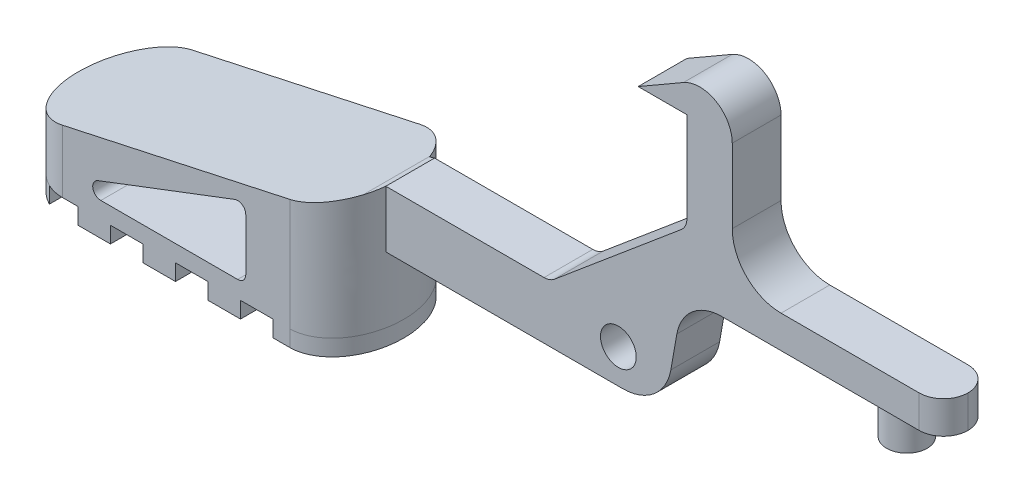
SolidWorks part; units mm, degrees
ref_plane "Alzado" through (0, 0, 0) normal (0, 0, 1) x (1, 0, 0)
ref_plane "Planta" through (0, 0, 0) normal (0, 1, 0) x (1, 0, 0)
ref_plane "Vista lateral" through (0, 0, 0) normal (1, 0, 0) x (0, 0, -1)
sketch "Croquis1" plane through (0, 0, 0) normal (0, 0, 1) x (1, 0, 0)
  line L0 (-3, -7.5922) -> (13, -7.5922)
  line L1 (13, -7.5922) -> (13, -5.5922)
  line L2 (13, -5.5922) -> (0, -5.5922)
  line L3 (-3, -7.5922) -> (-4.2155, -14.4859)
  line L4 (-4.2155, -14.4859) -> (-21.2155, -14.4859)
  line L5 (-21.2155, -14.4859) -> (-21.2155, -10.9859)
  line L6 (-21.2155, -10.9859) -> (-11.2155, -10.9859)
  line L7 (-11.2155, -10.9859) -> (-2.789, -3.9152)
  line L8 (-2.789, -3.9152) -> (-2.789, 2.0848)
  line L9 (-2.789, 2.0848) -> (-5.789, 2.0848)
  line L10 (-5.789, 2.0848) -> (0, 5.4271)
  line L11 (0, -5.5922) -> (0, 5.4271)
  dimension "D1" = 16
  dimension "D2" = 2
  dimension "D3" = 13
  dimension "D4" = 100
  dimension "D5" = 7
  dimension "D6" = 17
  dimension "D7" = 3.5
  dimension "D8" = 10
  dimension "D9" = 140
  dimension "D10" = 11
  dimension "D11" = 6
  dimension "D12" = 3
  dimension "D13" = 30
extrude "Saliente-Extruir1" add sketch "Croquis1" along normal blind 3
fillet "Redondeo1" radius 2 1 edges at (0, 5.4271, 1.5)
fillet "Redondeo2" radius 3 1 edges at (0, -5.5922, 1.5)
fillet "Redondeo3" radius 1.5 2 edges at (13, -6.5922, 3) (13, -6.5922, 0)
fillet "Redondeo4" radius 2.8 1 edges at (-3, -7.5922, 1.5)
fillet "Redondeo5" radius 1 2 edges at (-11.2155, -10.9859, 1.5) (-2.789, -3.9152, 1.5)
sketch "Croquis2" plane through (0, -7.5922, 0) normal (0, -1, 0) x (1, 0, 0)
  line L0 (10.5, 1.5084) -> (13, 1.5) construction
  circle A0 centre (9.25, 1.5084) radius 1.25
  dimension "D1" = 2.5
extrude "Saliente-Extruir2" add sketch "Croquis2" along normal blind 2.2
sketch "Croquis3" plane through (0, 0, 3) normal (0, 0, 1) x (1, 0, 0)
  line L0 (-5.9051, -12.3859) -> (-3.8453, -12.3859) construction
  line L1 (-4.2155, -14.4859) -> (-3.408, -9.906) construction
  line L2 (-7.0051, -13.4859) -> (-7.0051, -14.4859) construction
  line L3 (-21.2155, -14.4859) -> (-4.2155, -14.4859) construction
  circle A0 centre (-7.0051, -12.3859) radius 1.1
  dimension "D1" = 2.2
extrude "Cortar-Extruir1" cut sketch "Croquis3" against normal through all
fillet "Redondeo6" radius 3 1 edges at (-4.2155, -14.4859, 1.5)
sketch "Croquis4" plane through (0, 0, 3) normal (0, 0, 1) x (1, 0, 0)
  line L0 (-21.2155, -14.4859) -> (-21.2155, -18.5345)
  line L1 (-21.2155, -18.5345) -> (-41.2155, -18.5345)
  line L3 (-21.2155, -10.9859) -> (-21.2155, -14.4859)
  line L4 (-41.2155, -18.5345) -> (-41.2155, -15.3345)
  line L5 (-41.2155, -15.3345) -> (-21.2155, -10.9859)
  dimension "D1" = 3.2
extrude "Saliente-Extruir3" add sketch "Croquis4" along normal blind 3 separate body
sketch "Croquis5" plane through (0, 0, 3) normal (0, 0, -1) x (-1, 0, 0)
  line L6 (41.2155, -15.3345) -> (21.2155, -10.9859)
  line L7 (21.2155, -10.9859) -> (21.2155, -18.5345)
  line L8 (21.2155, -18.5345) -> (41.2155, -18.5345)
  line L10 (21.2155, -10.9859) -> (21.2155, -18.5345)
  line L11 (21.2155, -18.5345) -> (41.2155, -18.5345)
  line L13 (41.2155, -15.3345) -> (21.2155, -10.9859)
  line L14 (41.2155, -18.5345) -> (41.2155, -15.3345)
  line L15 (41.2155, -18.5345) -> (41.2155, -15.3345)
  dimension "D1" = 0
extrude "Saliente-Extruir4" add sketch "Croquis5" along normal blind 5
sketch "Croquis6" plane through (0, -18.5345, 0) normal (0, -1, 0) x (1, 0, 0)
  line L0 (-38.2155, 6) -> (-24.2155, 6) construction
  line L1 (-24.2155, 6) -> (-21.2155, 6)
  line L2 (-41.2155, 6) -> (-21.2155, 6) construction
  line L3 (-21.2155, 6) -> (-21.2155, 2)
  line L4 (-24.2155, 6) -> (-24.2155, -2) construction
  line L5 (-21.2155, -2) -> (-41.2155, -2) construction
  line L6 (-24.2155, -2) -> (-38.2155, -2) construction
  line L7 (-38.2155, -2) -> (-38.2155, 6) construction
  line L8 (-38.2155, 2) -> (-41.2155, 2) construction
  line L9 (-41.2155, -2) -> (-41.2155, 6) construction
  line L10 (-24.2155, 2) -> (-21.2155, 2) construction
  line L11 (-21.2155, -2) -> (-21.2155, 6) construction
  line L12 (-41.2155, 2) -> (-41.2155, 6)
  line L13 (-41.2155, 6) -> (-38.2155, 6)
  line L14 (-38.2155, -2) -> (-41.2155, -2)
  line L15 (-41.2155, -2) -> (-41.2155, 2)
  line L16 (-24.2155, -2) -> (-21.2155, -2)
  line L17 (-21.2155, -2) -> (-21.2155, 2)
  ellipse E0 centre (-38.2155, 2) end of major axis (-38.2155, -2) minor radius 3 (-38.2155, 6) -> (-41.2155, 2) ccw
  ellipse E1 centre (-38.2155, 2) end of major axis (-38.2155, -2) minor radius 3 (-38.2155, -2) -> (-41.2155, 2) cw
  ellipse E2 centre (-24.2155, 2) end of major axis (-24.2155, 6) minor radius 3 (-21.2155, 2) -> (-24.2155, 6) ccw
  ellipse E3 centre (-24.2155, 2) end of major axis (-24.2155, 6) minor radius 3 (-24.2155, -2) -> (-21.2155, 2) ccw
  dimension "D1" = 14
extrude "Cortar-Extruir2" cut sketch "Croquis6" against normal blind 5 contours L12 L13 E0
sketch "Croquis7" plane through (0, -18.5345, 0) normal (0, -1, 0) x (1, 0, 0)
  line L0 (-38.2155, -2) -> (-38.2155, 6) construction
  line L1 (-41.2155, 2) -> (-41.2155, -2)
  line L2 (-41.2155, -2) -> (-38.2155, -2)
  ellipse E0 centre (-38.2155, 2) end of major axis (-38.2155, -2) minor radius 3 (-38.2155, -2) -> (-41.2155, 2) cw
extrude "Cortar-Extruir3" cut sketch "Croquis7" against normal blind 5
sketch "Croquis8" plane through (0, -18.5345, 0) normal (0, -1, 0) x (1, 0, 0)
  line L0 (-24.2155, 6) -> (-24.2155, -2) construction
  line L1 (-24.2155, 6) -> (-21.2155, 6)
  line L2 (-21.2155, 6) -> (-21.2155, 2)
  ellipse E0 centre (-24.2155, 2) end of major axis (-24.2155, 6) minor radius 3 (-24.2155, 6) -> (-21.2155, 2) cw
extrude "Cortar-Extruir4" cut sketch "Croquis8" against normal through all
sketch "Croquis9" plane through (0, -18.5345, 0) normal (0, -1, 0) x (1, 0, 0)
  line L0 (-24.2155, 6) -> (-24.2155, -2) construction
  line L1 (-24.2155, -2) -> (-21.2155, -2)
  line L2 (-21.2155, -2) -> (-21.2155, 2)
  ellipse E0 centre (-24.2155, 2) end of major axis (-24.2155, 6) minor radius 3 (-24.2155, -2) -> (-21.2155, 2) ccw
extrude "Cortar-Extruir5" cut sketch "Croquis9" against normal through all
sketch "Croquis10" plane through (-21.2155, 0, 0) normal (-1, 0, 0) x (0, 0, 1)
  line L8 (3, -10.9859) -> (0, -10.9859)
  line L9 (0, -10.9859) -> (0, -14.4859)
  line L10 (0, -14.4859) -> (3, -14.4859)
  line L11 (3, -14.4859) -> (3, -10.9859)
  line L12 (3, -10.9859) -> (0, -10.9859)
  line L13 (0, -10.9859) -> (0, -14.4859)
  line L14 (0, -14.4859) -> (3, -14.4859)
  line L15 (3, -14.4859) -> (3, -10.9859)
  dimension "D1" = 0
extrude "Saliente-Extruir5" add sketch "Croquis10" along normal blind 1
sketch "Croquis12" plane through (0, 0, 3) normal (0, 0, 1) x (1, 0, 0)
  line L0 (-22.2155, -10.9859) -> (-22.2155, -11.2033)
  line L1 (-22.2155, -11.2033) -> (-21.3108, -11.0066)
  line L2 (-21.3108, -11.0066) -> (-21.3108, -10.9859)
  line L3 (-11.5795, -10.9859) -> (-22.2155, -10.9859) construction
  line L4 (-21.3108, -10.9859) -> (-22.2155, -10.9859)
extrude "Cortar-Extruir7" cut sketch "Croquis12" against normal through all
fillet "Redondeo7" radius 3 1 edges at (-21.3108, -11.0066, 1.5)
sketch "Croquis13" plane through (0, 0, 6) normal (0, 0, 1) x (1, 0, 0)
  line L0 (-26.9265, -13.8036) -> (-26.9265, -17.0095)
  line L1 (-27.4265, -17.5095) -> (-35.842, -17.5095)
  line L2 (-36.02, -16.5422) -> (-27.6045, -13.3363)
  arc A0 (-35.842, -17.5095) -> (-36.02, -16.5422) centre (-35.842, -17.0095) cw
  arc A1 (-26.9265, -13.8036) -> (-27.6045, -13.3363) centre (-27.4265, -13.8036) ccw
  arc A2 (-26.9265, -17.0095) -> (-27.4265, -17.5095) centre (-27.4265, -17.0095) cw
  dimension "D1" = 0.5
  dimension "D2" = 0.5
extrude "Cortar-Extruir8" cut sketch "Croquis13" against normal through all
sketch "Croquis14" plane through (0, -18.5345, 0) normal (0, -1, 0) x (1, 0, 0)
  line L0 (-39.251, -1.7542) -> (-39.251, 5.7542)
  line L3 (-39.251, 2) -> (-41.2155, 2) construction
  ellipse E0 centre (-38.2155, 2) end of major axis (-38.2155, -2) minor radius 3 (-38.2155, 6) -> (-38.2155, -2) ccw construction
  spline S0 degree 3 poles (-39.251, 5.7542) (-39.7861, 5.4916) (-40.4667, 4.7951) (-40.9621, 3.6978) (-41.2133, 2.6589) (-41.2465, 1.5628) (-40.9914, 0.3226) (-40.4164, -0.8701) (-39.7097, -1.5293) (-39.251, -1.7542) knots 0 0 0 0 0.199693 0.316984 0.40333 0.559671 0.682683 0.828477 1 1 1 1
extrude "Saliente-Extruir6" add sketch "Croquis14" along normal blind 1
sketch "Croquis15" plane through (0, -18.5345, 0) normal (0, -1, 0) x (1, 0, 0)
  line L0 (-38.2155, 6) -> (-24.2155, 6) construction
  line L1 (-37.251, 6) -> (-35.251, 6)
  line L2 (-37.251, 6) -> (-37.251, -2)
  line L3 (-37.251, -2) -> (-35.251, -2)
  line L4 (-35.251, 6) -> (-35.251, -2)
  line L5 (-24.2155, -2) -> (-38.2155, -2) construction
  line L6 (-39.251, -1.7542) -> (-39.251, 5.7542) construction
  dimension "D1" = 2
  dimension "D2" = 2
extrude "Saliente-Extruir7" add sketch "Croquis15" along normal blind 1
sketch "Croquis16" plane through (0, -18.5345, 0) normal (0, -1, 0) x (1, 0, 0)
  line L0 (-35.251, 6) -> (-24.2155, 6) construction
  line L1 (-33.251, 6) -> (-31.251, 6)
  line L2 (-33.251, 6) -> (-33.251, -2)
  line L3 (-33.251, -2) -> (-31.251, -2)
  line L4 (-31.251, 6) -> (-31.251, -2)
  line L5 (-24.2155, -2) -> (-35.251, -2) construction
  line L6 (-35.251, -2) -> (-35.251, 6) construction
  line L7 (-29.251, 6) -> (-27.251, 6)
  line L8 (-29.251, 6) -> (-29.251, -2)
  line L9 (-29.251, -2) -> (-27.251, -2)
  line L10 (-27.251, 6) -> (-27.251, -2)
  line L12 (-25.251, 6) -> (-25.251, -2)
  line L15 (-25.251, 6) -> (-24.2155, 6)
  line L16 (-25.251, -2) -> (-24.2155, -2)
  ellipse E0 centre (-24.2155, 2) end of major axis (-24.2155, 6) minor radius 3 (-24.2155, -2) -> (-24.2155, 6) ccw construction
  ellipse E1 centre (-24.2155, 2) end of major axis (-24.2155, 6) minor radius 3 (-21.6175, 0) -> (-21.3108, 3) ccw construction
  spline S0 degree 3 poles (-24.2155, -2) (-23.8492, -2.0014) (-23.2434, -1.8447) (-22.4384, -1.2852) (-21.7759, -0.4532) (-21.3591, 0.6043) (-21.1784, 1.7969) (-21.2496, 2.9391) (-21.5866, 4.0288) (-22.1197, 4.939) (-22.9536, 5.7369) (-23.7544, 6.0026) (-24.2155, 6) knots 0 0 0 0 0.099546 0.165341 0.2641 0.384419 0.470353 0.591126 0.692515 0.778153 0.876147 1 1 1 1
  dimension "D1" = 2
  dimension "D2" = 2
  dimension "D3" = 2
  dimension "D4" = 2
  dimension "D5" = 2
extrude "Saliente-Extruir8" add sketch "Croquis16" along normal blind 1
